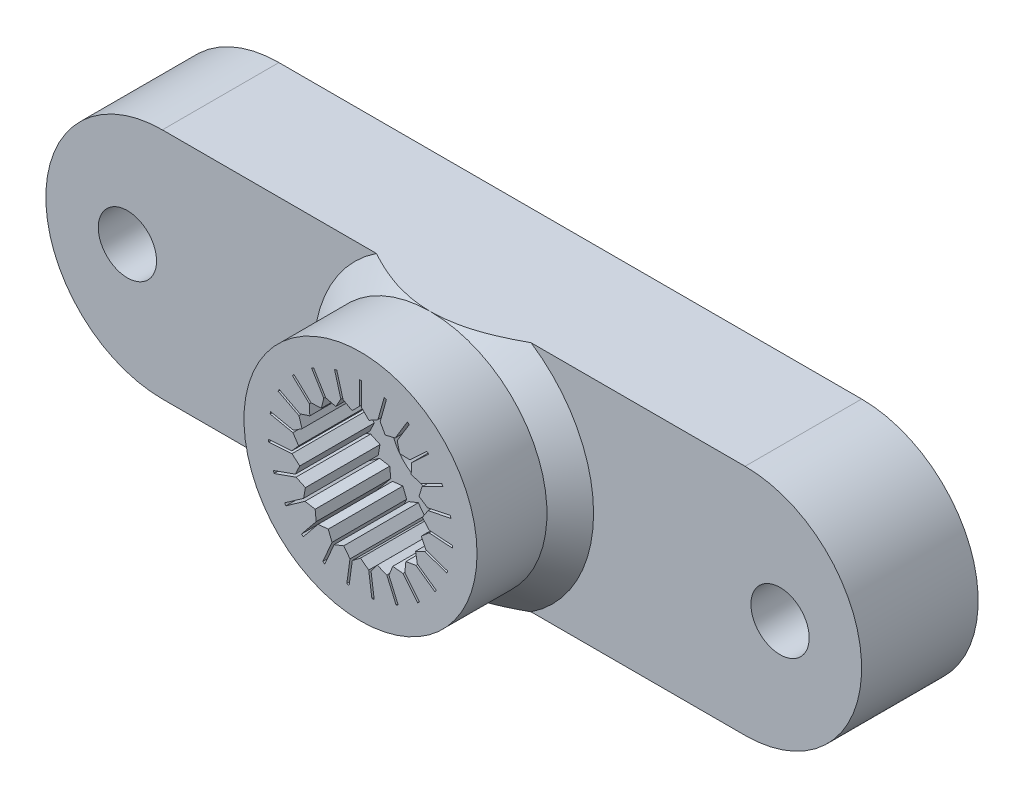
SolidWorks part; units mm, degrees
ref_plane "正面" through (0, 0, 0) normal (0, 0, 1) x (1, 0, 0)
ref_plane "平面" through (0, 0, 0) normal (0, 1, 0) x (1, 0, 0)
ref_plane "右側面" through (0, 0, 0) normal (1, 0, 0) x (0, 0, -1)
sketch "ｽｹｯﾁ1" plane through (0, 0, 0) normal (0, 0, 1) x (1, 0, 0)
  line L1 (12.5, -5) -> (-12.5, -5)
  line L2 (12.5, -5) -> (12.5, 5) construction
  line L3 (12.5, 5) -> (-12.5, 5)
  line L4 (-12.5, -5) -> (-12.5, 5) construction
  line L5 (12.5, -5) -> (-12.5, 5) construction
  line L6 (12.5, 5) -> (-12.5, -5) construction
  arc A0 (-12.5, 5) -> (-12.5, -5) centre (-12.5, 0) ccw
  arc A1 (12.5, 5) -> (12.5, -5) centre (12.5, 0) cw
  point P0 (0, 0)
  point P11 (0, 0)
  dimension "D1" = 10
  dimension "D2" = 25
extrude "ﾎﾞｽ - 押し出し1" add sketch "ｽｹｯﾁ1" along normal blind 5
sketch "ｽｹｯﾁ6" plane through (0, 0, 5) normal (0, 0, 1) x (1, 0, 0)
  circle A0 centre (0, 0) radius 5
  dimension "D1" = 10
extrude "ﾎﾞｽ - 押し出し3" add sketch "ｽｹｯﾁ6" along normal blind 4
sketch "ｽｹｯﾁ5" plane through (0, 0, 9) normal (0, 0, 1) x (1, 0, 0)
  line L0 (-0.3625, 2.6375) -> (0, 3) construction
  line L1 (0, 3) -> (0.3625, 2.6375) construction
  line L2 (-0.3625, 2.6375) -> (0, 0) construction
  line L3 (0, 0) -> (0.3625, 2.6375) construction
  line L4 (0, 3) -> (0, 0) construction
  line L5 (-0.05, 2.95) -> (-0.05, 3.95)
  line L6 (-0.05, 3.95) -> (0.05, 3.95)
  line L7 (0.05, 3.95) -> (0.05, 2.95)
  line L8 (-0.05, 2.95) -> (0.05, 2.95) construction
  line L9 (-0.3625, 2.6375) -> (-0.05, 2.95)
  line L10 (-0.05, 2.95) -> (0.05, 2.95) construction
  line L11 (0.3625, 2.6375) -> (0.05, 2.95)
  line L12 (0.3625, 2.6375) -> (0.7478, 2.8541)
  line L13 (0.7478, 2.8541) -> (1.0176, 3.817)
  line L14 (1.1138, 3.79) -> (0.844, 2.8271)
  line L15 (1.0607, 2.4419) -> (0.844, 2.8271)
  line L16 (1.0176, 3.817) -> (1.1138, 3.79)
  line L17 (1.0607, 2.4419) -> (1.4901, 2.5465)
  line L18 (1.4901, 2.5465) -> (2.0096, 3.4009)
  line L19 (2.0951, 3.349) -> (1.5755, 2.4946)
  line L20 (1.6801, 2.0652) -> (1.5755, 2.4946)
  line L21 (2.0096, 3.4009) -> (2.0951, 3.349)
  line L22 (1.6801, 2.0652) -> (2.1218, 2.0501)
  line L23 (2.1218, 2.0501) -> (2.8527, 2.7326)
  line L24 (2.9209, 2.6595) -> (2.1901, 1.977)
  line L25 (2.175, 1.5353) -> (2.1901, 1.977)
  line L26 (2.8527, 2.7326) -> (2.9209, 2.6595)
  line L27 (2.175, 1.5353) -> (2.5963, 1.4016)
  line L28 (2.5963, 1.4016) -> (3.4841, 1.8617)
  line L29 (3.5301, 1.7729) -> (2.6423, 1.3128)
  line L30 (2.5086, 0.8915) -> (2.6423, 1.3128)
  line L31 (3.4841, 1.8617) -> (3.5301, 1.7729)
  line L32 (2.5086, 0.8915) -> (2.8781, 0.6491)
  line L33 (2.8781, 0.6491) -> (3.8572, 0.8526)
  line L34 (3.8776, 0.7547) -> (2.8985, 0.5512)
  line L35 (2.6561, 0.1817) -> (2.8985, 0.5512)
  line L36 (3.8572, 0.8526) -> (3.8776, 0.7547)
  line L37 (2.6561, 0.1817) -> (2.9465, -0.1514)
  line L38 (2.9465, -0.1514) -> (3.9442, -0.2197)
  line L39 (3.9374, -0.3194) -> (2.9397, -0.2512)
  line L40 (2.6066, -0.5417) -> (2.9397, -0.2512)
  line L41 (3.9442, -0.2197) -> (3.9374, -0.3194)
  line L42 (2.6066, -0.5417) -> (2.7964, -0.9408)
  line L43 (2.7964, -0.9408) -> (3.7387, -1.2757)
  line L44 (3.7052, -1.3699) -> (2.7629, -1.035)
  line L45 (2.3638, -1.2248) -> (2.7629, -1.035)
  line L46 (3.7387, -1.2757) -> (3.7052, -1.3699)
  line L47 (2.3638, -1.2248) -> (2.4389, -1.6604)
  line L48 (2.4389, -1.6604) -> (3.2559, -2.237)
  line L49 (3.1982, -2.3187) -> (2.3812, -1.7421)
  line L50 (1.9457, -1.8171) -> (2.3812, -1.7421)
  line L51 (3.2559, -2.237) -> (3.1982, -2.3187)
  line L52 (1.9457, -1.8171) -> (1.9005, -2.2568)
  line L53 (1.9005, -2.2568) -> (2.5316, -3.0325)
  line L54 (2.454, -3.0956) -> (1.8229, -2.3199)
  line L55 (1.3833, -2.2747) -> (1.8229, -2.3199)
  line L56 (2.5316, -3.0325) -> (2.454, -3.0956)
  line L57 (1.3833, -2.2747) -> (1.2211, -2.6859)
  line L58 (1.2211, -2.6859) -> (1.6195, -3.6031)
  line L59 (1.5278, -3.6429) -> (1.1294, -2.7257)
  line L60 (0.7183, -2.5636) -> (1.1294, -2.7257)
  line L61 (1.6195, -3.6031) -> (1.5278, -3.6429)
  line L62 (0.7183, -2.5636) -> (0.4512, -2.9157)
  line L63 (0.4512, -2.9157) -> (0.5874, -3.9064)
  line L64 (0.4883, -3.92) -> (0.3522, -2.9293)
  line L65 (0, -2.6623) -> (0.3522, -2.9293)
  line L66 (0.5874, -3.9064) -> (0.4883, -3.92)
  line L67 (0, -2.6623) -> (-0.3522, -2.9293)
  line L68 (-0.3522, -2.9293) -> (-0.4883, -3.92)
  line L69 (-0.5874, -3.9064) -> (-0.4512, -2.9157)
  line L70 (-0.7183, -2.5636) -> (-0.4512, -2.9157)
  line L71 (-0.4883, -3.92) -> (-0.5874, -3.9064)
  line L72 (-0.7183, -2.5636) -> (-1.1294, -2.7257)
  line L73 (-1.1294, -2.7257) -> (-1.5278, -3.6429)
  line L74 (-1.6195, -3.6031) -> (-1.2211, -2.6859)
  line L75 (-1.3833, -2.2747) -> (-1.2211, -2.6859)
  line L76 (-1.5278, -3.6429) -> (-1.6195, -3.6031)
  line L77 (-1.3833, -2.2747) -> (-1.8229, -2.3199)
  line L78 (-1.8229, -2.3199) -> (-2.454, -3.0956)
  line L79 (-2.5316, -3.0325) -> (-1.9005, -2.2568)
  line L80 (-1.9457, -1.8171) -> (-1.9005, -2.2568)
  line L81 (-2.454, -3.0956) -> (-2.5316, -3.0325)
  line L82 (-1.9457, -1.8171) -> (-2.3812, -1.7421)
  line L83 (-2.3812, -1.7421) -> (-3.1982, -2.3187)
  line L84 (-3.2559, -2.237) -> (-2.4389, -1.6604)
  line L85 (-2.3638, -1.2248) -> (-2.4389, -1.6604)
  line L86 (-3.1982, -2.3187) -> (-3.2559, -2.237)
  line L87 (-2.3638, -1.2248) -> (-2.7629, -1.035)
  line L88 (-2.7629, -1.035) -> (-3.7052, -1.3699)
  line L89 (-3.7387, -1.2757) -> (-2.7964, -0.9408)
  line L90 (-2.6066, -0.5417) -> (-2.7964, -0.9408)
  line L91 (-3.7052, -1.3699) -> (-3.7387, -1.2757)
  line L92 (-2.6066, -0.5417) -> (-2.9397, -0.2512)
  line L93 (-2.9397, -0.2512) -> (-3.9374, -0.3194)
  line L94 (-3.9442, -0.2197) -> (-2.9465, -0.1514)
  line L95 (-2.6561, 0.1817) -> (-2.9465, -0.1514)
  line L96 (-3.9374, -0.3194) -> (-3.9442, -0.2197)
  line L97 (-2.6561, 0.1817) -> (-2.8985, 0.5512)
  line L98 (-2.8985, 0.5512) -> (-3.8776, 0.7547)
  line L99 (-3.8572, 0.8526) -> (-2.8781, 0.6491)
  line L100 (-2.5086, 0.8915) -> (-2.8781, 0.6491)
  line L101 (-3.8776, 0.7547) -> (-3.8572, 0.8526)
  line L102 (-2.5086, 0.8915) -> (-2.6423, 1.3128)
  line L103 (-2.6423, 1.3128) -> (-3.5301, 1.7729)
  line L104 (-3.4841, 1.8617) -> (-2.5963, 1.4016)
  line L105 (-2.175, 1.5353) -> (-2.5963, 1.4016)
  line L106 (-3.5301, 1.7729) -> (-3.4841, 1.8617)
  line L107 (-2.175, 1.5353) -> (-2.1901, 1.977)
  line L108 (-2.1901, 1.977) -> (-2.9209, 2.6595)
  line L109 (-2.8527, 2.7326) -> (-2.1218, 2.0501)
  line L110 (-1.6801, 2.0652) -> (-2.1218, 2.0501)
  line L111 (-2.9209, 2.6595) -> (-2.8527, 2.7326)
  line L112 (-1.6801, 2.0652) -> (-1.5755, 2.4946)
  line L113 (-1.5755, 2.4946) -> (-2.0951, 3.349)
  line L114 (-2.0096, 3.4009) -> (-1.4901, 2.5465)
  line L115 (-1.0607, 2.4419) -> (-1.4901, 2.5465)
  line L116 (-2.0951, 3.349) -> (-2.0096, 3.4009)
  line L117 (-1.0607, 2.4419) -> (-0.844, 2.8271)
  line L118 (-0.844, 2.8271) -> (-1.1138, 3.79)
  line L119 (-1.0176, 3.817) -> (-0.7478, 2.8541)
  line L120 (-0.3625, 2.6375) -> (-0.7478, 2.8541)
  line L121 (-1.1138, 3.79) -> (-1.0176, 3.817)
  circle A0 centre (0, 0) radius 3 construction
  circle A1 centre (0, 0) radius 2.6623 construction
  point P147 (0, 0)
  dimension "D1" = 6
  dimension "D2" = 7.826
  dimension "D3" = 7.826
  dimension "D4" = 0.1
  dimension "D5" = 1
  dimension "D6" = 23
extrude "ｶｯﾄ - 押し出し5" cut sketch "ｽｹｯﾁ5" against normal blind 3.2
chamfer "面取り1" distance 1 angle 45 2 edges at (-5, 0, 5) (5, 0, 5)
sketch "ｽｹｯﾁ7" plane through (0, 0, 0) normal (0, 0, -1) x (-1, 0, 0)
  circle A0 centre (14, 0) radius 1.25
  circle A1 centre (0, 0) radius 1.9
  circle A2 centre (-14, 0) radius 1.25
  point P7 (0, 0)
  point P8 (0, 0)
  point P9 (0, 0)
  dimension "D1" = 3.8
  dimension "D2" = 2.5
  dimension "D3" = 14
  dimension "D4" = 14
extrude "ｶｯﾄ - 押し出し6" cut sketch "ｽｹｯﾁ7" against normal through all both and the other way through all
equation "\"18.4.300mm\"=18.3"
equation "\"D2@ｽｹｯﾁ5\"=360deg/46"
equation "\"D3@ｽｹｯﾁ5\"=\"D2@ｽｹｯﾁ5\""
equation "\"D4@ｽｹｯﾁ7\"=\"D3@ｽｹｯﾁ7\""
